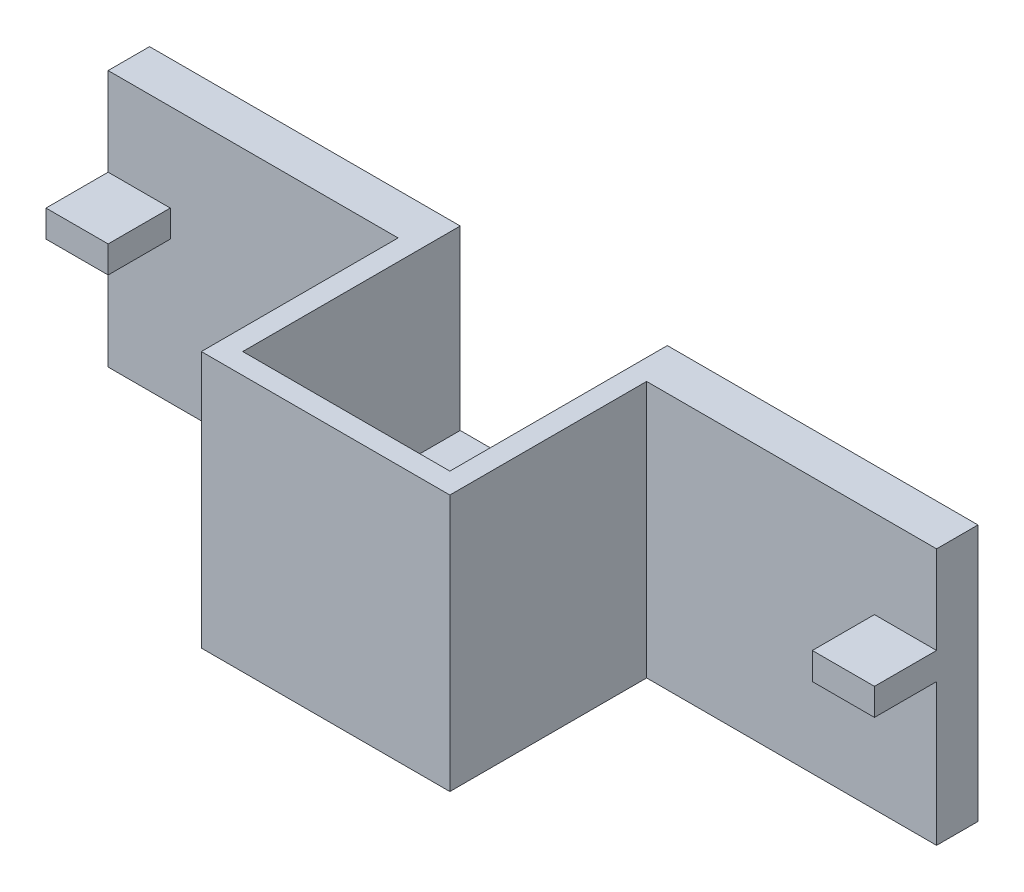
SolidWorks part; units mm, degrees
ref_plane "Front Plane" through (0, 0, 0) normal (0, 0, 1) x (1, 0, 0)
ref_plane "Top Plane" through (0, 0, 0) normal (0, 1, 0) x (1, 0, 0)
ref_plane "Right Plane" through (0, 0, 0) normal (1, 0, 0) x (0, 0, -1)
sketch "Sketch1" plane through (0, 0, 0) normal (0, 1, 0) x (1, 0, 0)
  line L1 (0, 0) -> (80, 0)
  line L2 (0, 0) -> (0, 4)
  line L3 (0, 4) -> (80, 4)
  line L4 (80, 0) -> (80, 4)
  dimension "D1" = 80
  dimension "D2" = 4
extrude "Boss-Extrude1" add sketch "Sketch1" along normal blind 24.8
sketch "Sketch2" plane through (0, 0, 0) normal (0, 0, 1) x (1, 0, 0)
  line L0 (0, 24.8) -> (80, 24.8) construction
  line L1 (0, 16.3) -> (6, 16.3)
  line L2 (0, 16.3) -> (0, 13.7)
  line L3 (0, 13.7) -> (6, 13.7)
  line L4 (6, 16.3) -> (6, 13.7)
  line L6 (40, 24.8) -> (40, 0) construction
  line L7 (0, 0) -> (80, 0) construction
  line L8 (80, 13.7) -> (74, 13.7)
  line L9 (74, 16.3) -> (74, 13.7)
  line L10 (80, 16.3) -> (74, 16.3)
  line L11 (80, 16.3) -> (80, 13.7)
  line L12 (0, 24.8) -> (0, 0) construction
  dimension "D1" = 2.6
  dimension "D2" = 6
  dimension "D3" = 8.5
extrude "Boss-Extrude2" add sketch "Sketch2" along normal blind 6
sketch "Sketch3" plane through (0, 0, 0) normal (0, 0, 1) x (1, 0, 0)
  line L0 (0, 0) -> (80, 0) construction
  line L1 (30, 0) -> (50, 0)
  line L2 (30, 0) -> (30, 24.8)
  line L3 (30, 24.8) -> (50, 24.8)
  line L4 (50, 0) -> (50, 24.8)
  line L5 (0, 24.8) -> (80, 24.8) construction
  line L6 (80, 13.7) -> (80, 0) construction
  line L7 (0, 13.7) -> (0, 0) construction
  dimension "D1" = 30
  dimension "D2" = 30
extrude "Cut-Extrude1" cut sketch "Sketch3" against normal blind 10
sketch "Sketch4" plane through (0, 0, 0) normal (0, -1, 0) x (1, 0, 0)
  line L0 (30, 0) -> (30, 17)
  line L1 (30, 17) -> (50, 17)
  line L2 (50, 17) -> (50, 0)
  line L3 (50, 0) -> (80, 0) construction
  line L4 (0, 0) -> (30, 0) construction
  dimension "D1" = 17
extrude "Extrude-Thin1" add sketch "Sketch4" against normal up to surface (24.8 mm away) thin up to face at (15, 24.8, -2) thin type one direction reverse wall 2
sketch "Sketch5" plane through (0, 0, 0) normal (0, -1, 0) x (1, 0, 0)
  line L1 (30, 17) -> (50, 17)
  line L2 (30, 17) -> (30, -4)
  line L3 (30, -4) -> (50, -4)
  line L4 (50, 17) -> (50, -4)
extrude "Boss-Extrude3" add sketch "Sketch5" against normal blind 7.7
